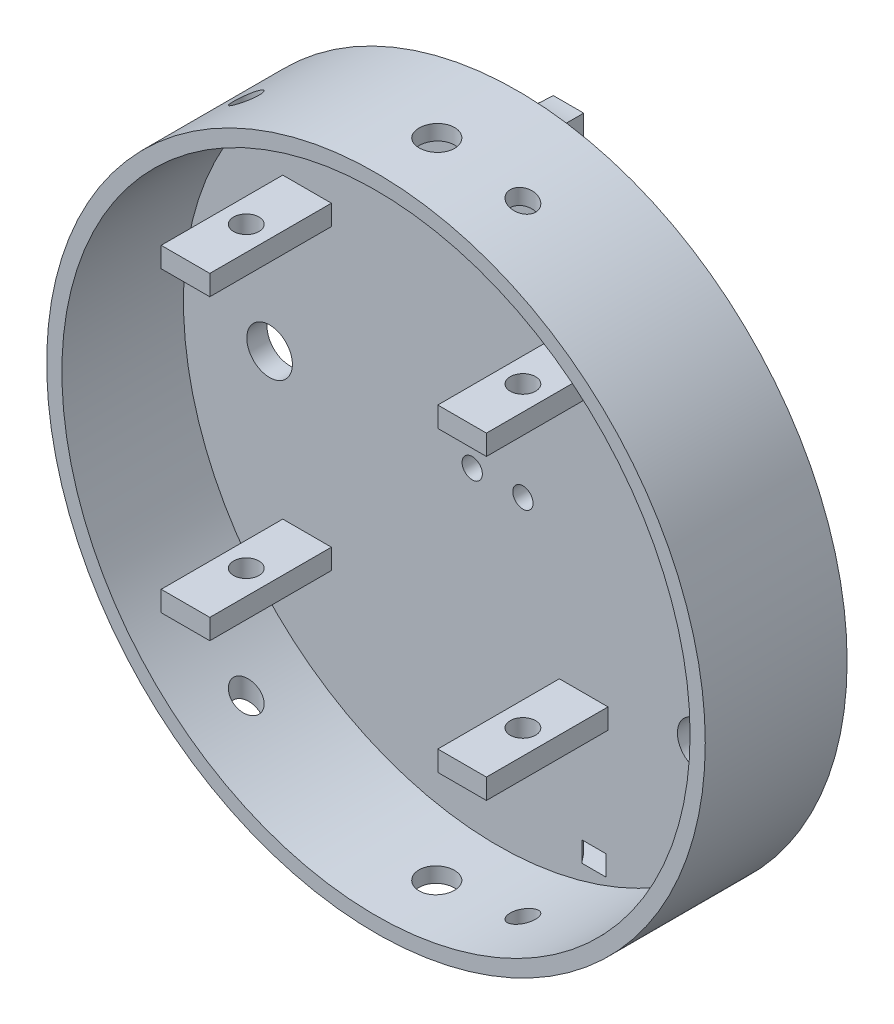
SolidWorks part; units mm, degrees
ref_plane "Alzado" through (0, 0, 0) normal (0, 0, 1) x (1, 0, 0)
ref_plane "Planta" through (0, 0, 0) normal (0, 1, 0) x (1, 0, 0)
ref_plane "Vista lateral" through (0, 0, 0) normal (1, 0, 0) x (0, 0, -1)
sketch "Croquis1" plane through (0, 0, 0) normal (0, 0, 1) x (1, 0, 0)
  line L0 (10, 20) -> (-10, 20) construction
  circle A0 centre (0, 0) radius 32.5
  circle A1 centre (-2.5, 0) radius 1
  circle A2 centre (2.5, 0) radius 1
  circle A3 centre (0, 20) radius 1
  circle A4 centre (10, 20) radius 1
  circle A5 centre (-10, 20) radius 1
  point P9 (0, 20)
  dimension "D1" = 65
  dimension "D4" = 2
  dimension "D7" = 2
  dimension "D2" = 2.5
  dimension "D3" = 2.5
  dimension "D5" = 20
  dimension "D6" = 20
extrude "Saliente-Extruir1" add sketch "Croquis1" along normal blind 2
sketch "Croquis2" plane through (0, 0, 2) normal (0, 0, 1) x (1, 0, 0)
  line L0 (-21.2, -15.7) -> (-16.4, -15.7)
  line L1 (10.9, -15.7) -> (6.1, -15.7)
  line L2 (-21.2, -15.7) -> (-21.2, -13.7)
  line L3 (-21.2, -13.7) -> (-16.4, -13.7)
  line L4 (-16.4, -13.7) -> (-16.4, -15.7)
  line L5 (6.1, -15.7) -> (6.1, -13.7)
  line L6 (6.1, -13.7) -> (10.9, -13.7)
  line L7 (10.9, -13.7) -> (10.9, -15.7)
  line L8 (6.1, -15.7) -> (10.9, -15.7)
  line L9 (0, 0) -> (12.8027, 0) construction
  line L10 (10.9, 13.7) -> (10.9, 15.7)
  line L11 (10.9, 15.7) -> (6.1, 15.7)
  line L12 (6.1, 13.7) -> (10.9, 13.7)
  line L13 (6.1, 15.7) -> (6.1, 13.7)
  line L14 (-16.4, 13.7) -> (-16.4, 15.7)
  line L15 (-21.2, 15.7) -> (-16.4, 15.7)
  line L16 (-21.2, 15.7) -> (-21.2, 13.7)
  line L17 (-21.2, 13.7) -> (-16.4, 13.7)
  point P2 (0, -15.7)
  point P3 (-16.4, -15.7)
  point P13 (8.5, -15.7)
  point P16 (8.5, 15.7)
  dimension "D1" = 32.1
  dimension "D2" = 10.9
  dimension "D3" = 15.7
  dimension "D4" = 4.8
  dimension "D5" = 4.8
  dimension "D6" = 2
  dimension "D7" = 2
extrude "Saliente-Extruir2" add sketch "Croquis2" along normal blind 12 contours L7 L6 L5 L1 | L4 L3 L2 L0 | L16 L17 L14 L15 | L11 L13 L12 L10 region at (-18.8, -14.7, 2) region at (8.5, -14.7, 2) region at (8.5, 14.7, 2) region at (-18.8, 14.7, 2)
sketch "Croquis3" plane through (0, -15.7, 0) normal (0, -1, 0) x (1, 0, 0)
  line L0 (-18.8, 14) -> (-18.8, 2) construction
  line L1 (-21.2, 14) -> (-16.4, 14) construction
  line L2 (-21.2, 2) -> (-16.4, 2) construction
  line L3 (8.5, 14) -> (8.5, 2) construction
  line L4 (10.9, 14) -> (6.1, 14) construction
  line L5 (10.9, 2) -> (6.1, 2) construction
  circle A0 centre (-18.8, 8) radius 1.25
  circle A1 centre (8.5, 8) radius 1.25
  dimension "D1" = 2.5
extrude "Cortar-Extruir1" cut sketch "Croquis3" against normal up to surface (31.4 mm away) up to face at (8.5, 15.7, 8)
ref_plane "Plano1" through (0, -32.5, 0) normal (0, -1, 0) x (-1, 0, 0)
ref_plane "Plano2" through (0, -28.35, 0) normal (0, -1, 0) x (-1, 0, 0)
sketch "Croquis5" plane through (0, -28.35, 0) normal (0, -1, 0) x (-1, 0, 0)
  line L0 (-8.5, -8) -> (18.8, -8) construction
  line L1 (0, 0) -> (0, -8) construction
  line L2 (-32.5, -2) -> (32.5, -2) construction
  line L3 (-10.68, -2) -> (-8.3104, -2)
  line L4 (32.5, 0) -> (-32.5, 0) construction
  line L5 (9.277, 0) -> (6.408, 0)
  line L6 (8.3104, -2) -> (10.68, -2)
  line L7 (-6.408, 0) -> (-9.277, 0)
  arc A0 (-9.277, 0) -> (-10.68, -2) centre (0, -8) ccw
  arc A1 (-6.408, 0) -> (-8.3104, -2) centre (0, -8) ccw
  arc A2 (10.68, -2) -> (9.277, 0) centre (0, -8) ccw
  arc A3 (8.3104, -2) -> (6.408, 0) centre (0, -8) ccw
  dimension "D1" = 24.5
  dimension "D2" = 20.5
extrude "Cortar-Extruir3" cut sketch "Croquis5" against normal blind 2
mirror "Simetría1" about plane through (0, 0, 0) normal (0, 1, 0) of "Cortar-Extruir3"
sketch "Croquis6" plane through (0, 0, 0) normal (0, 0, -1) x (-1, 0, 0)
  circle A0 centre (-20, 12.5) radius 2.25
  circle A1 centre (-20, -12.5) radius 2.25
  circle A2 centre (22.5, 0) radius 2.25
  dimension "D1" = 4.5
  dimension "D2" = 4.5
  dimension "D3" = 4.5
  dimension "D6" = 25
  dimension "D7" = 12.5
  dimension "D4" = 22.5
  dimension "D5" = 20
extrude "Cortar-Extruir4" cut sketch "Croquis6" against normal blind 2.5
sketch "Croquis7" plane through (0, 0, 2) normal (0, 0, 1) x (1, 0, 0)
  circle A2 centre (0, 0) radius 32.5 construction
  circle A9 centre (0, 0) radius 32.5
  circle A11 centre (0, 0) radius 31
  dimension "D1" = 1.5
extrude "Saliente-Extruir3" add sketch "Croquis7" along normal blind 12
ref_plane "Plano3" through (0, -32.5, 0) normal (0, -1, 0) x (-1, 0, 0)
sketch "Croquis8" plane through (0, -32.5, 0) normal (0, -1, 0) x (-1, 0, 0)
  circle A0 centre (-8.5, -8) radius 1.25 construction
  circle A1 centre (-8.5, -8) radius 1.25
  circle A2 centre (18.8, -8) radius 1.25 construction
  circle A3 centre (18.8, -8) radius 1.25
  circle A4 centre (0, -8) radius 1.75
  dimension "D1" = 3.5
extrude "Cortar-Extruir5" cut sketch "Croquis8" against normal blind 70
sketch "Sketch1" plane through (0, 0, 0) normal (0, 0, -1) x (-1, 0, 0)
  line L0 (6.408, 26.35) -> (6.408, 28.35) construction
  line L1 (-1.502, 28.85) -> (1.498, 28.85)
  line L2 (-1.502, 28.85) -> (-1.502, 25.85)
  line L3 (-1.502, 25.85) -> (1.498, 25.85)
  line L4 (1.498, 28.85) -> (1.498, 25.85)
  line L5 (-1.502, 28.85) -> (1.498, 25.85) construction
  line L6 (-1.502, 25.85) -> (1.498, 28.85) construction
  line L7 (0, 0) -> (-11.4103, 0) construction
  line L8 (-1.502, -25.85) -> (1.498, -28.85) construction
  line L9 (-1.502, -28.85) -> (1.498, -25.85) construction
  line L10 (1.498, -28.85) -> (1.498, -25.85)
  line L11 (-1.502, -25.85) -> (1.498, -25.85)
  line L12 (-1.502, -28.85) -> (-1.502, -25.85)
  line L13 (-1.502, -28.85) -> (1.498, -28.85)
  line L14 (-6.408, -26.35) -> (-6.408, -28.35) construction
  point P0 (-0.002, 27.35)
  point P8 (6.408, 27.35)
  point P15 (-0.002, -27.35)
  dimension "D1" = 4.91
  dimension "D2" = 3
  dimension "D3" = 3
  dimension "D4" = 4.906
extrude "Boss-Extrude1" add sketch "Sketch1" along normal blind 5
fillet "Fillet1" radius 2 6 edges at (1.502, 27.35, 0) (-1.498, -27.35, 0) (0.002, 25.85, 0) (0.002, 28.85, 0) (0.002, -25.85, 0) (0.002, -28.85, 0) second distance 5 first distance on face at (0.002, 27.35, 0)
sketch "Sketch2" plane through (0, 0, 2) normal (0, 0, 1) x (1, 0, 0)
  line L1 (-10.68, -26.35) -> (-5.6668, -26.35)
  line L2 (-10.68, -26.35) -> (-10.68, -28.75)
  line L3 (-10.68, -28.75) -> (-5.6668, -28.75)
  line L4 (-5.6668, -26.35) -> (-5.6668, -28.75)
  line L5 (10.68, 26.35) -> (5.4941, 26.35)
  line L6 (10.68, 26.35) -> (10.68, 28.75)
  line L7 (10.68, 28.75) -> (5.4941, 28.75)
  line L8 (5.4941, 26.35) -> (5.4941, 28.75)
extrude "Tapon" add sketch "Sketch2" against normal up to surface (2 mm away) up to face at (1.002, 25.6, 0)
equation "\"D2@Croquis6\"=\"D1@Croquis6\""
equation "\"D3@Croquis6\"=\"D1@Croquis6\""
equation "\"D7@Croquis6\"=\"D6@Croquis6\"/2"
